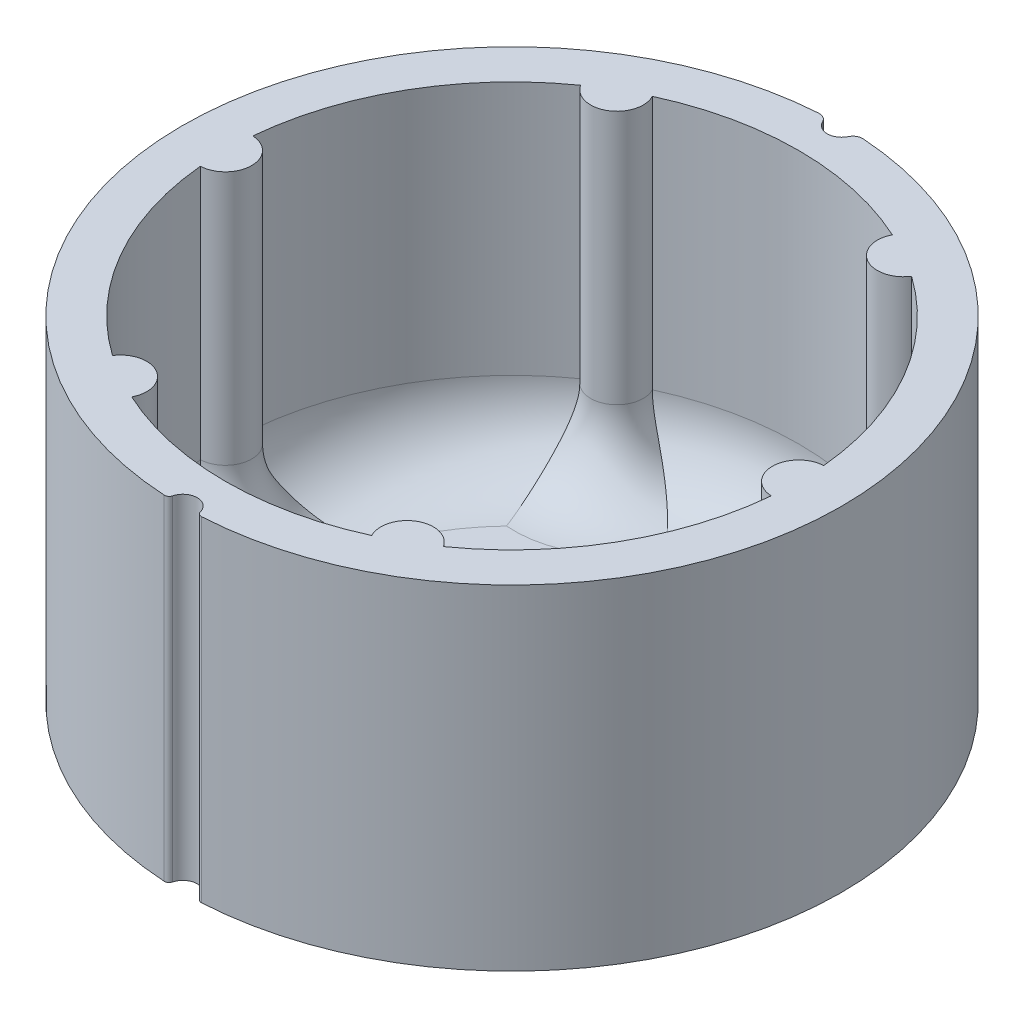
SolidWorks part; units mm, degrees
ref_plane "Front Plane" through (0, 0, 0) normal (0, 0, 1) x (1, 0, 0)
ref_plane "Top Plane" through (0, 0, 0) normal (0, 1, 0) x (1, 0, 0)
ref_plane "Right Plane" through (0, 0, 0) normal (1, 0, 0) x (0, 0, -1)
sketch "Sketch1" plane through (0, 0, 0) normal (0, 1, 0) x (1, 0, 0)
  line L3 (0, 0.002) -> (0, 3.7877) construction
  line L4 (0, 3.7877) -> (2.417, 3.7877)
  line L5 (0, 3.7877) -> (-2.417, 3.7877)
  arc A0 (1.9642, -34.442) -> (34.1982, 4.5552) centre (0, 0.002) ccw
  arc A2 (-2.417, 3.7877) -> (2.417, 3.7877) centre (0, 0.002) ccw
  circle A3 centre (0, 0.002) radius 34.5 construction
  arc A7 (-1.3541, 33.8562) -> (1.3541, 33.8562) centre (0, 34.5015) ccw
  arc A8 (34.1982, 4.5552) -> (2.3241, 34.4236) centre (0, 0.002) ccw
  arc A9 (-2.3241, 34.4236) -> (-34.1982, 4.5552) centre (0, 0.002) ccw
  arc A10 (-34.1982, 4.5552) -> (-1.9642, -34.442) centre (0, 0.002) ccw
  arc A11 (1.3541, 33.8562) -> (2.3241, 34.4236) centre (2.2568, 33.4259) cw
  arc A12 (-1.3541, 33.8562) -> (-2.3241, 34.4236) centre (-2.2568, 33.4259) ccw
  arc A13 (1.4518, -34.0686) -> (-1.4518, -34.0686) centre (0, -34.4457) ccw
  arc A14 (1.4518, -34.0686) -> (1.9642, -34.442) centre (1.9358, -33.9428) ccw
  arc A15 (-1.4518, -34.0686) -> (-1.9642, -34.442) centre (-1.9358, -33.9428) cw
  point P15 (1.4997, 34.4694)
  dimension "D2" = 4.834
  dimension "D3" = 4.4915
  dimension "D4" = 34.5
  dimension "D5" = 1
  dimension "D6" = 1.5
  dimension "D7" = 0.5
  dimension "D11" = 1.4997
sketch "Sketch2" plane through (0, 0, 0) normal (0, 1, 0) x (1, 0, 0)
  arc A16 (-17.316, 24.4981) -> (-29.874, 2.7471) centre (0, 0) ccw
  circle A23 centre (0, 0) radius 27.25 construction
  arc A24 (29.874, 2.7471) -> (29.874, -2.7471) centre (30, 0) ccw
  arc A25 (17.316, -24.4981) -> (12.5579, -27.2452) centre (15, -25.9808) ccw
  arc A26 (-12.5579, -27.2452) -> (-17.316, -24.4981) centre (-15, -25.9808) ccw
  arc A27 (-29.874, -2.7471) -> (-29.874, 2.7471) centre (-30, 0) ccw
  arc A28 (-17.316, 24.4981) -> (-12.5579, 27.2452) centre (-15, 25.9808) ccw
  arc A29 (12.5579, 27.2452) -> (17.316, 24.4981) centre (15, 25.9808) ccw
  arc A30 (-29.874, -2.7471) -> (-17.316, -24.4981) centre (0, 0) ccw
  arc A31 (-12.5579, -27.2452) -> (12.5579, -27.2452) centre (0, 0) ccw
  arc A32 (17.316, -24.4981) -> (29.874, -2.7471) centre (0, 0) ccw
  arc A33 (29.874, 2.7471) -> (17.316, 24.4981) centre (0, 0) ccw
  arc A34 (12.5579, 27.2452) -> (-12.5579, 27.2452) centre (0, 0) ccw
  dimension "D1" = 60
  dimension "D2" = 54.5
  dimension "D3" = 6
extrude "Boss-Extrude1" add sketch "Sketch1" along normal blind 35 contours A10 A0 A8 A7 A9 A2 L5 L4 region at (2.2155, 0, 33.5591)
extrude "Cut-Extrude2" cut sketch "Sketch2" along normal through all
extrude "Boss-Extrude2" add sketch "Sketch2<2>" along normal blind 0.4
sketch "Sketch2<2>" plane through (0, 0, 0) normal (0, 1, 0) x (1, 0, 0) same geometry as "Sketch2"
fillet "Fillet1" radius 8 12 edges at (13.625, 0.4, 23.5992) (0, 0.4, 30) (-13.625, 0.4, 23.5992) (-25.9808, 0.4, 15) (-27.25, 0.4, 0) (-25.9808, 0.4, -15) (-13.625, 0.4, -23.5992) (0, 0.4, -30) (13.625, 0.4, -23.5992) (25.9808, 0.4, -15) (27.25, 0.4, 0) (25.9808, 0.4, 15)
equation "\"2.5.00mm\"=3"
